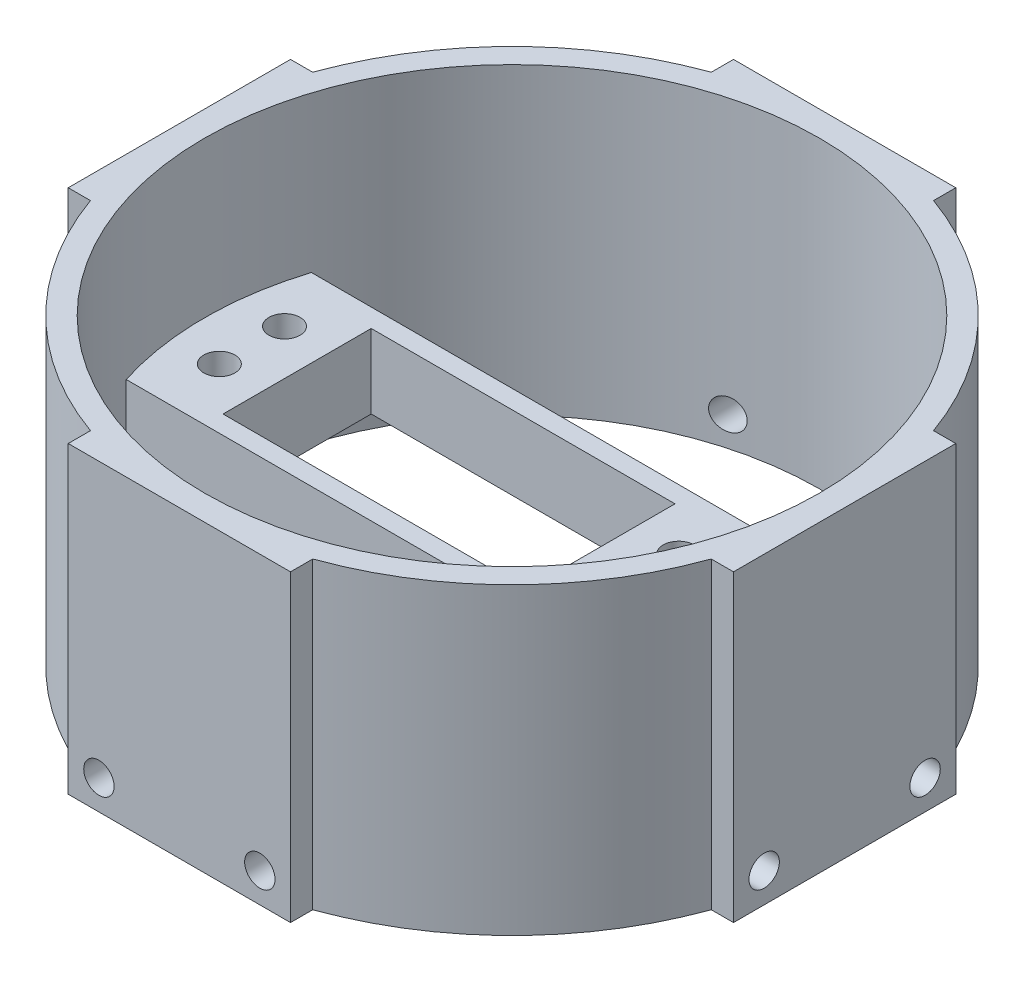
SolidWorks part; units mm, degrees
ref_plane "Front Plane" through (0, 0, 0) normal (0, 0, 1) x (1, 0, 0)
ref_plane "Top Plane" through (0, 0, 0) normal (0, 1, 0) x (1, 0, 0)
ref_plane "Right Plane" through (0, 0, 0) normal (1, 0, 0) x (0, 0, -1)
sketch "Sketch1" plane through (0, 0, 0) normal (0, 1, 0) x (1, 0, 0)
  circle A0 centre (0, 0) radius 44.5
  circle A1 centre (0, 0) radius 41.5
  dimension "D1" = 3
  dimension "D2" = 83
extrude "Boss-Extrude1" add sketch "Sketch1" along normal blind 41
sketch "Sketch2" plane through (0, 0, 0) normal (0, 1, 0) x (1, 0, 0)
  line L0 (-39.5727, 12.5) -> (39.5727, 12.5)
  line L1 (-39.5727, -12.5) -> (39.5727, -12.5)
  line L2 (-8.5, 10) -> (-8.5, -15.818) construction
  line L3 (-29, 10) -> (12, 10)
  line L4 (-29, 10) -> (-29, -10)
  line L5 (-29, -10) -> (12, -10)
  line L6 (12, 10) -> (12, -10)
  circle A0 centre (0, 0) radius 41.5 construction
  arc A1 (-39.5727, 12.5) -> (-39.5727, -12.5) centre (-3.1584, 0) ccw
  arc A2 (39.5727, 12.5) -> (39.5727, -12.5) centre (3.1584, 0) cw
  circle A3 centre (18.1, 4.4) radius 2.1
  circle A4 centre (18.1, -4.4) radius 2.1
  circle A7 centre (-35.1, 4.4) radius 2.1
  circle A8 centre (-35.1, -4.4) radius 2.1
  point P6 (0, 0)
  dimension "D5" = 4.2
  dimension "D6" = 4.4
  dimension "D7" = 4.4
  dimension "D11" = 0
  dimension "D1" = 12.5
  dimension "D2" = 12.5
  dimension "D3" = 20
  dimension "D4" = 41
  dimension "D8" = 10
  dimension "D9" = 12
  dimension "D10" = 6.1
extrude "Boss-Extrude2" add sketch "Sketch2" along normal blind 20
sketch "Sketch3" plane through (0, 0, 0) normal (0, 1, 0) x (1, 0, 0)
  line L0 (0, 0) -> (0, 56.6556) construction
  line L1 (0, 44.8957) -> (-15, 44.8957)
  line L2 (-15, 44.8957) -> (-15, 41.8957)
  line L3 (0, 44.8957) -> (15, 44.8957)
  line L4 (15, 44.8957) -> (15, 41.8957)
  circle A0 centre (0, 0) radius 44.5 construction
  arc A1 (-15, 41.8957) -> (15, 41.8957) centre (0, 0) cw
  dimension "D1" = 15
  dimension "D2" = 15
  dimension "D3" = 3
extrude "Boss-Extrude3" add sketch "Sketch3" along normal blind 41
pattern_circular "CirPattern1" count 4 over 360 about axis through (0, 41, 0) along (0, -1, 0) of "Boss-Extrude3"
sketch "Sketch4" plane through (-44.8957, 0, 0) normal (-1, 0, 0) x (0, 0, 1)
  line L1 (0, 37.0728) -> (0, -4.8522) construction
  line L2 (-15, 0) -> (15, 0) construction
  line L3 (15, 41) -> (15, 0) construction
  circle A0 centre (10.8598, 4) radius 2.05
  circle A2 centre (-10.8598, 4) radius 2.05
  dimension "D1" = 4
  dimension "D2" = 4.1
  dimension "D3" = 4.1402
extrude "Cut-Extrude1" cut sketch "Sketch4" against normal blind 7
sketch "Sketch5" plane through (0, 0, 0) normal (0, 1, 0) x (1, 0, 0)
  line L0 (-39.5727, 12.5) -> (39.5727, 12.5)
  line L1 (-39.5727, -12.5) -> (39.5727, -12.5)
  arc A0 (-39.5727, 12.5) -> (-39.5727, -12.5) centre (0, 0) ccw
  arc A1 (39.5727, -12.5) -> (39.5727, 12.5) centre (0, 0) ccw
extrude "Cut-Extrude2" cut sketch "Sketch5" along normal blind 10
pattern_circular "CirPattern2" count 4 every 90 about axis through (0, 41, 0) along (0, -1, 0) of "Cut-Extrude1"
